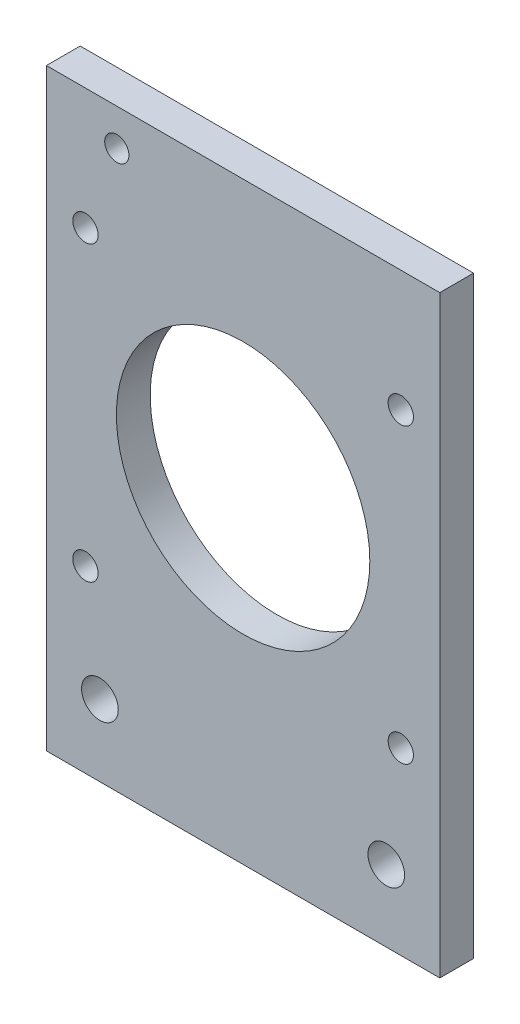
SolidWorks part; units mm, degrees
ref_plane "Front Plane" through (0, 0, 0) normal (0, 0, 1) x (1, 0, 0)
ref_plane "Top Plane" through (0, 0, 0) normal (0, 1, 0) x (1, 0, 0)
ref_plane "Right Plane" through (0, 0, 0) normal (1, 0, 0) x (0, 0, -1)
sketch "Sketch2" plane through (0, 0, 0) normal (0, 0, 1) x (1, 0, 0)
  line L0 (-55, 48.4) -> (55, 48.4) construction
  line L1 (-34.925, 0) -> (34.925, 0)
  line L2 (-34.925, 0) -> (-34.925, 57.9)
  line L3 (-34.925, 57.9) -> (34.925, 57.9) construction
  line L4 (34.925, 0) -> (34.925, 57.9)
  line L5 (0, 48.4) -> (0, 0) construction
  line L6 (0, 48.4) -> (0, 57.9) construction
  line L7 (-34.925, 25.4) -> (34.925, 25.4) construction
  line L10 (34.925, 90.4) -> (-34.925, 90.4) construction
  line L11 (34.925, 57.9) -> (34.925, 90.4)
  line L12 (34.925, 90.4) -> (-34.925, 90.4) construction
  line L13 (-34.925, 90.4) -> (-34.925, 57.9)
  line L14 (34.925, 90.4) -> (34.925, 105.4)
  line L15 (34.925, 105.4) -> (-34.925, 105.4)
  line L16 (-34.925, 90.4) -> (-34.925, 105.4)
  line L17 (-34.925, 25.4) -> (34.925, 25.4) construction
  circle A0 centre (-55, 48.4) radius 3 construction
  circle A1 centre (55, 48.4) radius 3 construction
  circle A2 centre (-55, 48.4) radius 15 construction
  circle A3 centre (55, 48.4) radius 15 construction
  circle A6 centre (0, 57.9) radius 22.5
  circle A7 centre (-55, 48.4) radius 15.6 construction
  point P6 (0, 0)
  dimension "D1" = 6
  dimension "D2" = 30
  dimension "D5" = 45
  dimension "D9" = 15
  dimension "D3" = 110
  dimension "D4" = 9.5
  dimension "D6" = 69.85
  dimension "D7" = 0.6
  dimension "D8" = 32.5
  dimension "D10" = 25.4
  dimension "D12" = 32.5
extrude "Boss-Extrude1" add sketch "Sketch2" along normal mid plane 6
sketch "Sketch3" plane through (0, 0, 3) normal (0, 0, 1) x (1, 0, 0)
  line L0 (34.925, 105.4) -> (-34.925, 105.4) construction
  line L1 (-34.925, 0) -> (-25.425, 0) construction
  line L2 (-34.925, 0) -> (-34.925, 12.7) construction
  line L3 (-34.925, 12.7) -> (-25.425, 12.7) construction
  line L4 (-25.425, 0) -> (-25.425, 12.7) construction
  line L5 (34.925, 0) -> (25.425, 0) construction
  line L6 (34.925, 0) -> (34.925, 12.7) construction
  line L7 (34.925, 12.7) -> (25.425, 12.7) construction
  line L8 (25.425, 0) -> (25.425, 12.7) construction
  line L11 (-34.925, 105.4) -> (-34.925, 0) construction
  circle A0 centre (-25.425, 12.7) radius 3.2576
  circle A1 centre (25.425, 12.7) radius 3.2576
  circle A4 centre (-22.425, 98.9) radius 2.15
  dimension "D1" = 12.7
  dimension "D2" = 6.5151
  dimension "D7" = 4.3
  dimension "D3" = 9.5
  dimension "D8" = 12.5
  dimension "D9" = 6.5
extrude "Cut-Extrude1" cut sketch "Sketch3" against normal blind 6
sketch "Sketch4" plane through (0, 0, 3) normal (0, 0, 1) x (1, 0, 0)
  circle A0 centre (-28, 31.9) radius 2.25 construction
  circle A1 centre (28, 83.9) radius 2.25 construction
  circle A2 centre (-28, 83.9) radius 2.25 construction
  circle A3 centre (-28, 31.9) radius 2.25
  circle A4 centre (28, 83.9) radius 2.25
  circle A5 centre (-28, 83.9) radius 2.25
  circle A6 centre (28, 31.9) radius 2.25
extrude "Cut-Extrude2" cut sketch "Sketch4" against normal blind 10
